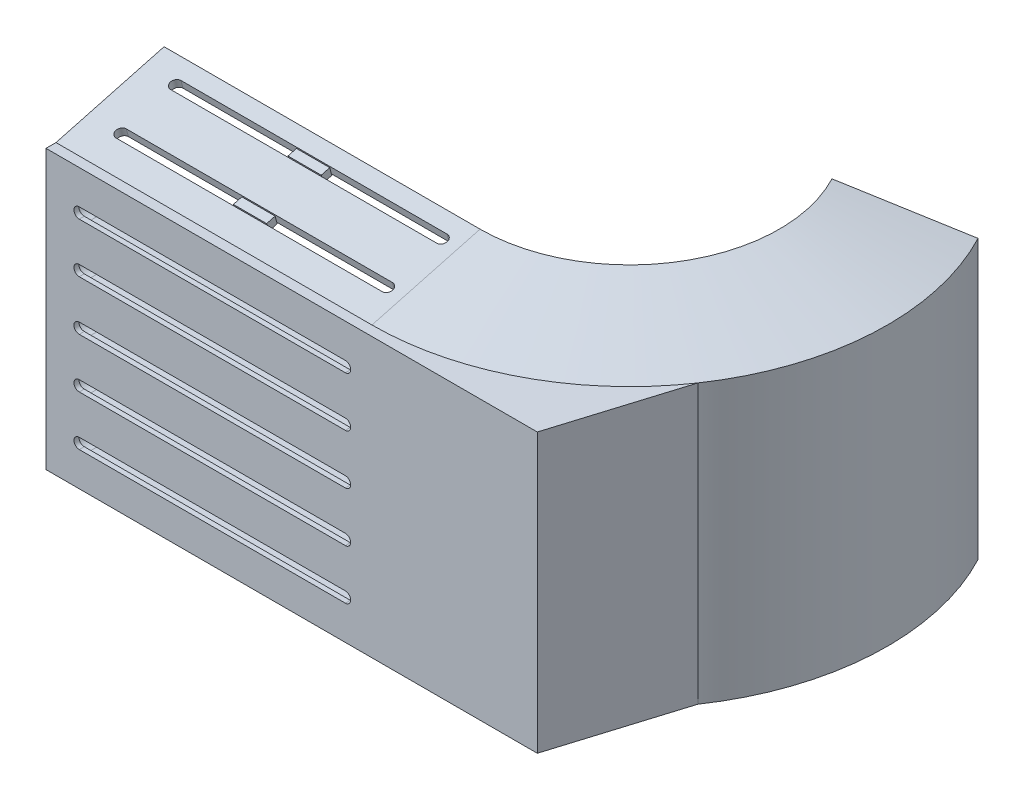
SolidWorks part; units mm, degrees
ref_plane "Front Plane" through (0, 0, 0) normal (0, 0, 1) x (1, 0, 0)
ref_plane "Top Plane" through (0, 0, 0) normal (0, 1, 0) x (1, 0, 0)
ref_plane "Right Plane" through (0, 0, 0) normal (1, 0, 0) x (0, 0, -1)
sketch "Sketch2" plane through (0, 0, 0) normal (0, 1, 0) x (1, 0, 0)
  line L0 (0, 0) -> (95, 0)
  line L2 (161.3325, 110) -> (95, 75) construction
  line L3 (95, 75) -> (170, 75) construction
  arc A0 (95, 0) -> (161.3325, 110) centre (95, 75) ccw
  dimension "D1" = 95
  dimension "D2" = 110
  dimension "D3" = 75
sketch "Sketch4" plane through (0, 0, 0) normal (1, 0, 0) x (0, 0, -1)
  line L0 (0, -40) -> (0, 40)
  line L1 (0, -40) -> (30, -48.0385)
  line L2 (30, -48.0385) -> (30, -50.5385)
  line L3 (30, -50.5385) -> (-2.5, -41.8301)
  line L4 (-2.5, -41.8301) -> (-2.5, 41.8301)
  line L5 (-2.5, 41.8301) -> (30, 50.5385)
  line L6 (30, 50.5385) -> (30, 48.0385)
  line L7 (30, 48.0385) -> (0, 40)
  line L8 (0, 0) -> (-2.5, 0) construction
  point P2 (0, 0)
  dimension "D1" = 2.5
  dimension "D2" = 80
  dimension "D3" = 30
  dimension "D4" = 105
sweep "Sweep1" add profiles "Sketch4" path "Sketch2"
sketch "Sketch6" plane through (53, 0, 2.5) normal (0, 0, -1) x (-1, 0, 0)
  line L0 (43, 30) -> (-37, 30) construction
  line L1 (43, 28.4) -> (-37, 28.4)
  line L2 (43, 31.6) -> (-37, 31.6)
  line L3 (43, 0) -> (-37, 0) construction
  line L5 (43, -1.6) -> (-37, -1.6)
  line L6 (43, 1.6) -> (-37, 1.6)
  line L7 (43, -30) -> (-37, -30) construction
  line L8 (43, -31.6) -> (-37, -31.6)
  line L9 (43, -28.4) -> (-37, -28.4)
  line L10 (43, -15) -> (-37, -15) construction
  line L11 (43, -16.6) -> (-37, -16.6)
  line L12 (43, -13.4) -> (-37, -13.4)
  line L13 (43, 15) -> (-37, 15) construction
  line L14 (43, 13.4) -> (-37, 13.4)
  line L15 (43, 16.6) -> (-37, 16.6)
  line L16 (3, 30) -> (3, 15) construction
  line L17 (3, 15) -> (3, 0) construction
  line L18 (3, 0) -> (3, -15) construction
  line L19 (3, -15) -> (3, -30) construction
  line L21 (53, 41.8301) -> (53, -41.8301) construction
  line L22 (-42, 41.8301) -> (-42, -41.8301) construction
  arc A0 (43, 28.4) -> (43, 31.6) centre (43, 30) ccw
  arc A1 (-37, 31.6) -> (-37, 28.4) centre (-37, 30) ccw
  arc A2 (43, -1.6) -> (43, 1.6) centre (43, 0) ccw
  arc A3 (-37, 1.6) -> (-37, -1.6) centre (-37, 0) ccw
  arc A4 (43, -31.6) -> (43, -28.4) centre (43, -30) ccw
  arc A5 (-37, -28.4) -> (-37, -31.6) centre (-37, -30) ccw
  arc A6 (43, -16.6) -> (43, -13.4) centre (43, -15) ccw
  arc A7 (-37, -13.4) -> (-37, -16.6) centre (-37, -15) ccw
  arc A8 (43, 13.4) -> (43, 16.6) centre (43, 15) ccw
  arc A9 (-37, 16.6) -> (-37, 13.4) centre (-37, 15) ccw
  point P2 (3, 30)
  point P7 (3, 0)
  point P16 (3, -30)
  point P23 (3, -15)
  point P30 (3, 15)
  point P50 (-42, 0)
  dimension "D1" = 3.2
  dimension "D2" = 15
  dimension "D3" = 5
  dimension "D4" = 10
extrude "Cut-Extrude1" cut sketch "Sketch6" along normal up to surface (2.5 mm away) up to face at (47.5, 0, 0)
sketch "Sketch7" plane through (50, 0, 2.5) normal (0, 0, -1) x (-1, 0, 0)
  line L0 (-45, 41.8301) -> (-45, -41.8301) construction
  line L1 (-45, 41.8301) -> (50, 41.8301)
  line L2 (-45, 41.8301) -> (-45, -41.8301)
  line L3 (-45, -41.8301) -> (50, -41.8301)
  line L4 (50, 41.8301) -> (50, -41.8301)
  line L5 (50, 41.8301) -> (50, -41.8301) construction
  line L6 (-40, 30) -> (40, 30) construction
  line L7 (-40, 31.6) -> (40, 31.6)
  line L8 (-40, 28.4) -> (40, 28.4)
  line L9 (-40, 15) -> (40, 15) construction
  line L10 (-40, 16.6) -> (40, 16.6)
  line L11 (-40, 13.4) -> (40, 13.4)
  line L12 (40, 0) -> (-40, 0) construction
  line L13 (40, -1.6) -> (-40, -1.6)
  line L14 (40, 1.6) -> (-40, 1.6)
  line L15 (-40, -15) -> (40, -15) construction
  line L16 (-40, -13.4) -> (40, -13.4)
  line L17 (-40, -16.6) -> (40, -16.6)
  line L18 (-40, -30) -> (40, -30) construction
  line L19 (-40, -28.4) -> (40, -28.4)
  line L20 (-40, -31.6) -> (40, -31.6)
  line L21 (40, -28.4) -> (-40, -28.4) construction
  line L22 (40, -13.4) -> (-40, -13.4) construction
  line L23 (40, 1.6) -> (-40, 1.6) construction
  line L24 (40, 16.6) -> (-40, 16.6) construction
  line L25 (-40, 28.4) -> (40, 28.4) construction
  line L27 (50, 41.8301) -> (-45, 41.8301) construction
  arc A0 (-40, 31.6) -> (-40, 28.4) centre (-40, 30) ccw
  arc A1 (40, 28.4) -> (40, 31.6) centre (40, 30) ccw
  arc A2 (-40, 16.6) -> (-40, 13.4) centre (-40, 15) ccw
  arc A3 (40, 13.4) -> (40, 16.6) centre (40, 15) ccw
  arc A4 (40, -1.6) -> (40, 1.6) centre (40, 0) ccw
  arc A5 (-40, 1.6) -> (-40, -1.6) centre (-40, 0) ccw
  arc A6 (-40, -13.4) -> (-40, -16.6) centre (-40, -15) ccw
  arc A7 (40, -16.6) -> (40, -13.4) centre (40, -15) ccw
  arc A8 (-40, -28.4) -> (-40, -31.6) centre (-40, -30) ccw
  arc A9 (40, -31.6) -> (40, -28.4) centre (40, -30) ccw
  point P6 (-45, 0)
  point P7 (-45, 0)
  point P14 (0, 30)
  point P19 (0, 15)
  point P28 (0, 0)
  point P37 (0, -15)
  point P46 (0, -30)
extrude "Boss-Extrude1" add sketch "Sketch7" against normal blind 3
sketch "Sketch9" plane through (50, 0, 0) normal (0, 0, -1) x (-1, 0, 0)
  line L0 (-40, 30) -> (40, 30) construction
  line L1 (-40, 33.6) -> (40, 33.6)
  line L2 (-40, 26.4) -> (40, 26.4)
  line L3 (-40, 15) -> (40, 15) construction
  line L4 (-40, 18.6) -> (40, 18.6)
  line L5 (-40, 11.4) -> (40, 11.4)
  line L6 (-40, 0) -> (40, 0) construction
  line L7 (-40, 3.6) -> (40, 3.6)
  line L8 (-40, -3.6) -> (40, -3.6)
  line L9 (-40, -15) -> (40, -15) construction
  line L10 (-40, -11.4) -> (40, -11.4)
  line L11 (-40, -18.6) -> (40, -18.6)
  line L12 (-40, -30) -> (40, -30) construction
  line L13 (-40, -26.4) -> (40, -26.4)
  line L14 (-40, -33.6) -> (40, -33.6)
  line L16 (-40, 28.4) -> (40, 28.4) construction
  arc A0 (-40, 33.6) -> (-40, 26.4) centre (-40, 30) ccw
  arc A1 (40, 26.4) -> (40, 33.6) centre (40, 30) ccw
  arc A2 (-40, 18.6) -> (-40, 11.4) centre (-40, 15) ccw
  arc A3 (40, 11.4) -> (40, 18.6) centre (40, 15) ccw
  arc A4 (-40, 3.6) -> (-40, -3.6) centre (-40, 0) ccw
  arc A5 (40, -3.6) -> (40, 3.6) centre (40, 0) ccw
  arc A6 (-40, -11.4) -> (-40, -18.6) centre (-40, -15) ccw
  arc A7 (40, -18.6) -> (40, -11.4) centre (40, -15) ccw
  arc A8 (-40, -26.4) -> (-40, -33.6) centre (-40, -30) ccw
  arc A9 (40, -33.6) -> (40, -26.4) centre (40, -30) ccw
  point P4 (0, 30)
  point P9 (0, 15)
  point P18 (0, 0)
  point P27 (0, -15)
  point P36 (0, -30)
  dimension "D1" = 2
extrude "Cut-Extrude2" cut sketch "Sketch9" against normal blind 4
sketch "Sketch10" plane through (51.866, 52.6195, -37.7667) normal (0, -0.9659, -0.2588) x (0, -0.2588, 0.9659)
  line L0 (14.7406, 41.866) -> (14.7406, -38.134) construction
  line L1 (16.3406, 41.866) -> (16.3406, -38.134)
  line L2 (13.1406, 41.866) -> (13.1406, -38.134)
  line L3 (31.7406, 41.866) -> (31.7406, -38.134) construction
  line L4 (33.3406, 41.866) -> (33.3406, -38.134)
  line L5 (30.1406, 41.866) -> (30.1406, -38.134)
  line L6 (8.0406, 51.866) -> (8.0406, -43.134) construction
  line L7 (45.7838, 41.866) -> (47.2326, 41.866) construction
  line L8 (45.7838, -38.134) -> (47.2326, -38.134) construction
  arc A0 (16.3406, 41.866) -> (13.1406, 41.866) centre (14.7406, 41.866) ccw
  arc A1 (13.1406, -38.134) -> (16.3406, -38.134) centre (14.7406, -38.134) ccw
  arc A2 (33.3406, 41.866) -> (30.1406, 41.866) centre (31.7406, 41.866) ccw
  arc A3 (30.1406, -38.134) -> (33.3406, -38.134) centre (31.7406, -38.134) ccw
  point P2 (14.7406, 1.866)
  point P7 (31.7406, 1.866)
  dimension "D1" = 5.1
  dimension "D2" = 17
  dimension "D3" = 3.2
extrude "Cut-Extrude3" cut sketch "Sketch10" along normal up to surface (105.1563 mm away)
chamfer "Chamfer1" distance 370 angle 45 1 edges at (95, 0, 2.5)
sketch "Sketch13" plane through (0, 39.653, 10.625) normal (0, 0.9659, 0.2588) x (1, 0, 0)
  line L0 (90, 33.7581) -> (10, 33.7581) construction
  line L1 (45, 19.6781) -> (55, 19.6781)
  line L2 (45, 19.6781) -> (45, 17.0381)
  line L3 (45, 17.0381) -> (55, 17.0381)
  line L4 (55, 19.6781) -> (55, 17.0381)
  line L5 (45, 36.6781) -> (55, 36.6781)
  line L6 (45, 36.6781) -> (45, 34.0381)
  line L7 (45, 34.0381) -> (55, 34.0381)
  line L8 (55, 36.6781) -> (55, 34.0381)
  line L9 (45, 34.0381) -> (45, 33.7581) construction
  line L10 (45, 36.6781) -> (45, 36.9581) construction
  line L11 (10, 36.9581) -> (90, 36.9581) construction
  line L12 (45, 19.9581) -> (45, 19.6781) construction
  line L13 (10, 19.9581) -> (90, 19.9581) construction
  line L14 (45, 17.0381) -> (45, 16.7581) construction
  line L15 (90, 16.7581) -> (10, 16.7581) construction
  point P15 (50, 16.7581)
  point P21 (50, 17.0381)
  point P22 (47.0074, 36.9581)
  point P23 (0, 0)
  dimension "D1" = 0.28
  dimension "D2" = 10
extrude "Boss-Extrude2" add sketch "Sketch13" against normal up to surface (2.4148 mm away) separate body up to face at (47.5, 44.0192, -15)
mirror "Mirror1" about plane through (0, 0, 0) normal (0, 1, 0) of "Cut-Extrude3"
mirror "Mirror3" about plane through (0, 0, 0) normal (0, 1, 0) of bodies 109 108
